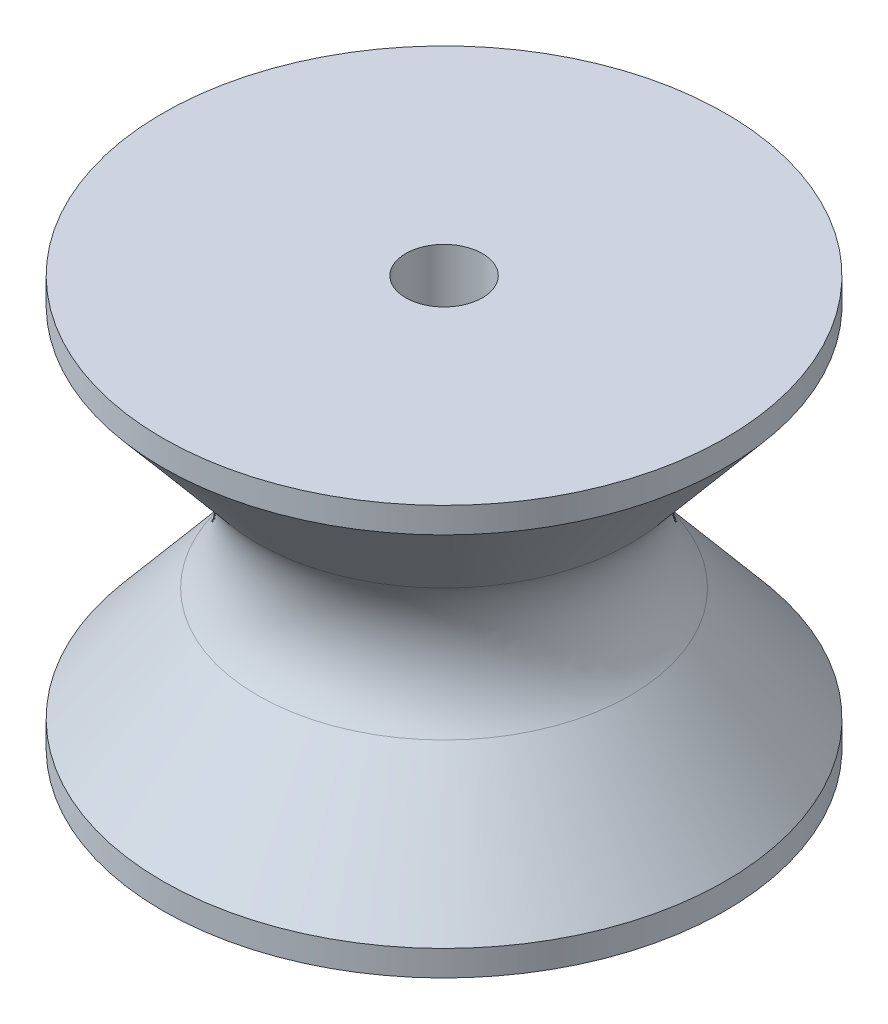
SolidWorks part; units mm, degrees
material "ABS"
ref_plane "Front" through (0, 0, 0) normal (0, 0, 1) x (1, 0, 0)
ref_plane "Top" through (0, 0, 0) normal (0, 1, 0) x (1, 0, 0)
ref_plane "Right" through (0, 0, 0) normal (1, 0, 0) x (0, 0, -1)
sketch "Esquisse1" plane through (0, 0, 0) normal (0, 0, 1) x (1, 0, 0)
  line L0 (-3.174, 0) -> (-0.75, 0) construction
  line L1 (-0.75, -4) -> (-0.75, 4)
  line L2 (-0.75, 4) -> (-5.5, 4)
  line L3 (-5.5, 4) -> (-5.5, 3.5)
  line L4 (-5.5, 3.5) -> (-3.6419, 1.2856)
  line L5 (-5.5, -3.5) -> (-3.6419, -1.2856)
  line L6 (-5.5, -4) -> (-5.5, -3.5)
  line L7 (-0.75, -4) -> (-5.5, -4)
  line L8 (0, 4) -> (0, -4) construction
  arc A0 (-3.6419, 1.2856) -> (-3.6419, -1.2856) centre (-5.174, 0) cw
  point P17 (-3.174, 0)
  dimension "D1" = 8
  dimension "D4" = 2
  dimension "D2" = 1.5
  dimension "D3" = 11
  dimension "D5" = 0.5
  dimension "D6" = 100
  dimension "D7" = 6.3479
revolve "Révolution1" add sketch "Esquisse1" angle 360 about L8
sketch "Esquisse2" plane through (0, -4, 0) normal (0, -1, 0) x (1, 0, 0)
  circle A1 centre (0, 0) radius 0.75 construction
  circle A2 centre (0, 0) radius 0.75
extrude "Boss.-Extru.1" [suppressed] add sketch "Esquisse2" against normal blind 0.2
